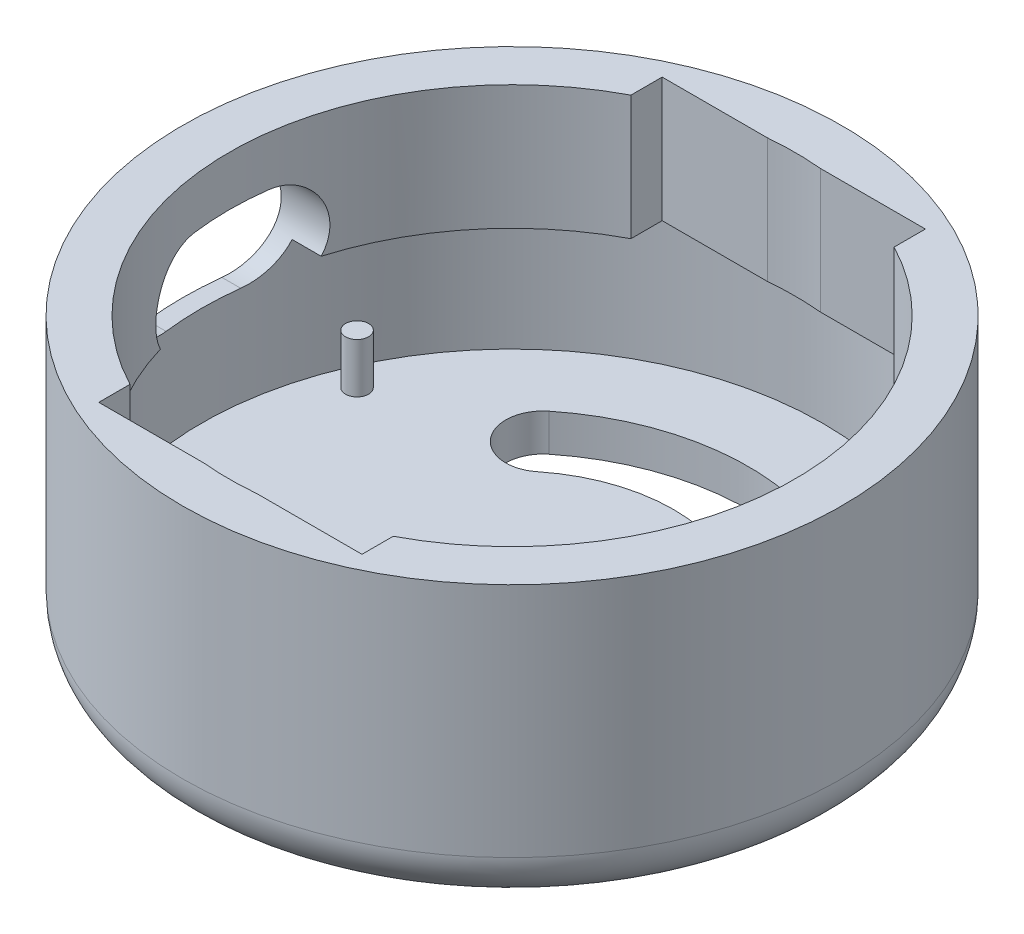
SolidWorks part; units mm, degrees
note: The reader was unsure of these and kept them because the rebuilt part matched: shared geometry of "Sketch1<3>".
ref_plane "Front Plane" through (0, 0, 0) normal (0, 0, 1) x (1, 0, 0)
ref_plane "Top Plane" through (0, 0, 0) normal (0, 1, 0) x (1, 0, 0)
ref_plane "Right Plane" through (0, 0, 0) normal (1, 0, 0) x (0, 0, -1)
sketch "Sketch1" plane through (0, 0, 0) normal (0, 1, 0) x (1, 0, 0)
  circle A0 centre (0, 0) radius 25
  circle A1 centre (0, 0) radius 26.5
  dimension "D1" = 50
  dimension "D2" = 53
extrude "Boss-Extrude1" add sketch "Sketch1" along normal blind 3 contours A1 A0
extrude "Boss-Extrude2" add sketch "Sketch1<3>" along normal blind 10 from surface at 3 starting at face at (0, 3, 26.5)
sketch "Sketch1<3>" plane through (0, 0, 0) normal (0, 1, 0) x (1, 0, 0) same geometry as "Sketch1"
sketch "Sketch2" plane through (0, 3, 0) normal (0, 1, 0) x (1, 0, 0)
  line L0 (-7.15, 0) -> (7.15, 0) construction
  arc A4 (-10, 12.49) -> (10, 12.49) centre (0, 0) cw construction
  arc A5 (11.875, 14.8319) -> (-11.875, 14.8319) centre (0, 0) ccw
  arc A6 (8.125, 10.1481) -> (-8.125, 10.1481) centre (0, 0) ccw
  arc A7 (8.125, 10.1481) -> (11.875, 14.8319) centre (10, 12.49) ccw
  arc A8 (-11.875, 14.8319) -> (-8.125, 10.1481) centre (-10, 12.49) ccw
  arc A9 (-10, -12.49) -> (10, -12.49) centre (0, 0) ccw construction
  arc A10 (11.875, -14.8319) -> (-11.875, -14.8319) centre (0, 0) cw
  arc A11 (8.125, -10.1481) -> (-8.125, -10.1481) centre (0, 0) cw
  arc A12 (8.125, -10.1481) -> (11.875, -14.8319) centre (10, -12.49) cw
  arc A13 (-11.875, -14.8319) -> (-8.125, -10.1481) centre (-10, -12.49) cw
  point P3 (-10.5942, 8.5458)
  point P4 (0, 16)
  point P9 (0, 0)
  point P10 (0, 0)
  point P11 (0, 0)
  point P16 (0, -16)
  point P22 (0, 0)
  point P23 (0, 0)
  point P24 (10.9783, 8.0337)
  point P25 (12.6831, 9.7539)
  point P26 (0, 0)
  dimension "D2" = 16
  dimension "D1" = 3
  dimension "D3" = 20
extrude "Cut-Extrude1" cut sketch "Sketch2" against normal through all
sketch "Sketch3" plane through (0, 13, 0) normal (0, 1, 0) x (1, 0, 0)
  line L1 (-10.5819, -22.65) -> (10.5819, -22.65)
  line L2 (-10.5819, -22.65) -> (-10.5819, 22.65)
  line L3 (-10.5819, 22.65) -> (10.5819, 22.65)
  line L4 (10.5819, -22.65) -> (10.5819, 22.65)
  line L5 (-10.5819, -22.65) -> (10.5819, 22.65) construction
  line L6 (-10.5819, 22.65) -> (10.5819, -22.65) construction
  circle A0 centre (0, 0) radius 22.75
  circle A1 centre (0, 0) radius 26.5
  circle M2 centre (0, 0) radius 26.5
  circle M3 centre (0, 0) radius 25
  dimension "D1" = 50
  dimension "D2" = 45.3
extrude "Boss-Extrude3" add sketch "Sketch3" along normal blind 10 contours A0 L2 M3 | M2 M3 | A0 L3 M3 | A0 L4 M3 | A0 L1 M3
sketch "Sketch5" plane through (0, 3, -3) normal (0, -1, 0) x (1, 0, 0)
  line B0 (22.625, 13.2) -> (-22.625, 13.2)
  line B1 (-22.625, 13.2) -> (-22.625, -7.2)
  line B2 (-22.625, -7.2) -> (22.625, -7.2)
  line B3 (22.625, -7.2) -> (22.625, 13.2)
  line B4 (0, 13.2) -> (0, -7.2) construction
  circle B5 centre (-21.225, 11.76) radius 0.925
  circle B6 centre (21.225, 11.76) radius 0.925
  circle B7 centre (-21.225, -5.76) radius 0.925
  circle B8 centre (21.225, -5.76) radius 0.925
  circle M18 centre (21.265, 12.2753) radius 0.7681
  circle M19 centre (21.265, -6.2753) radius 0.7681
  circle M20 centre (-21.265, 12.2753) radius 0.7681
  circle M21 centre (-21.265, -6.2753) radius 0.75
sketch_block_instance "Block2-1"
sketch_block "Block2"
sketch_block_instance "Block1-1"
sketch_block "Block1"
extrude "Boss-Extrude5" add sketch "Sketch5" against normal blind 4 contours B7 M21 | B7 M21 | B5 M20 | B5 M20 | B6 M18 | B6 M18 | B8 M19 | B8 M19
fillet "Fillet1" radius 4 1 edges at (0, 0, 26.5)
sketch "Sketch6" plane through (0, 0, 0) normal (1, 0, 0) x (0, 0, -1)
  line L0 (-3, 15) -> (3, 15) construction
  line L1 (-3, 19) -> (3, 19)
  line L2 (-3, 11) -> (3, 11)
  line L3 (26.5, 23) -> (-26.5, 23) construction
  arc A0 (-3, 19) -> (-3, 11) centre (-3, 15) ccw
  arc A1 (3, 11) -> (3, 19) centre (3, 15) ccw
  point P2 (0, 15)
  point P7 (0, 0)
  dimension "D2" = 4
  dimension "D1" = 6
  dimension "D3" = 8
extrude "Cut-Extrude2" cut sketch "Sketch6" against normal blind 44
